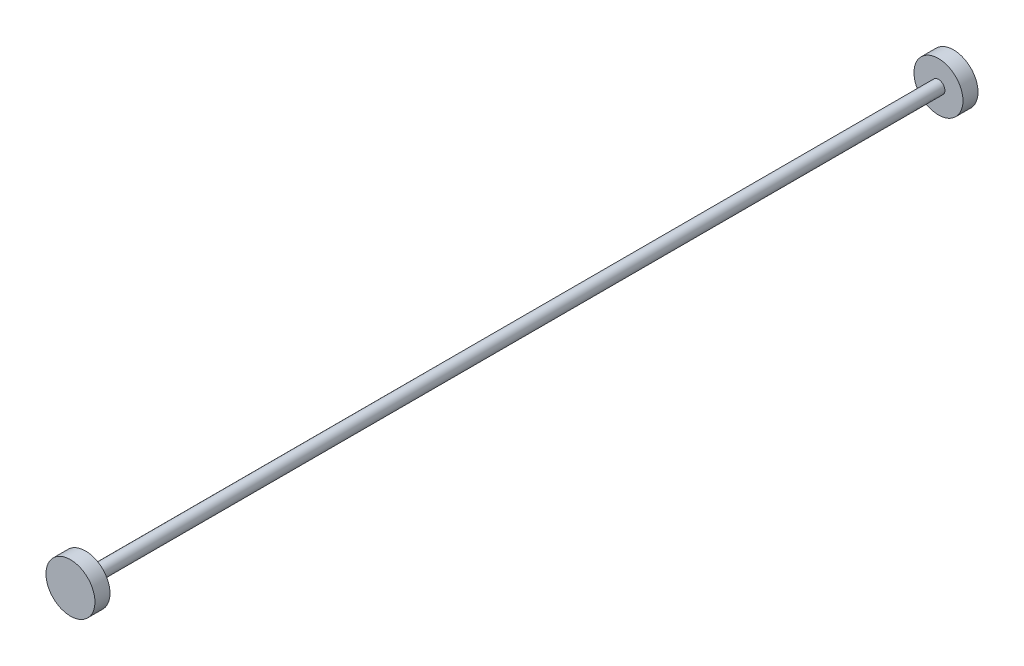
SolidWorks part; units mm, degrees
ref_plane "Front Plane" through (0, 0, 0) normal (0, 0, 1) x (1, 0, 0)
ref_plane "Top Plane" through (0, 0, 0) normal (0, 1, 0) x (1, 0, 0)
ref_plane "Right Plane" through (0, 0, 0) normal (1, 0, 0) x (0, 0, -1)
sketch "Sketch1" plane through (0, 0, 0) normal (0, 0, 1) x (1, 0, 0)
  circle A0 centre (0, 0) radius 2.44
  dimension "D1" = 4.88
extrude "Boss-Extrude1" add sketch "Sketch1" along normal blind 1.5
sketch "Sketch2" plane through (0, 0, 1.5) normal (0, 0, 1) x (1, 0, 0)
  circle A0 centre (0, 0) radius 0.64
  dimension "D1" = 1.28
extrude "Boss-Extrude2" add sketch "Sketch2" along normal blind 85
pattern_linear "LPattern2" count 2 spacing 86.5 along (0, 0, 1) of "Boss-Extrude1"
